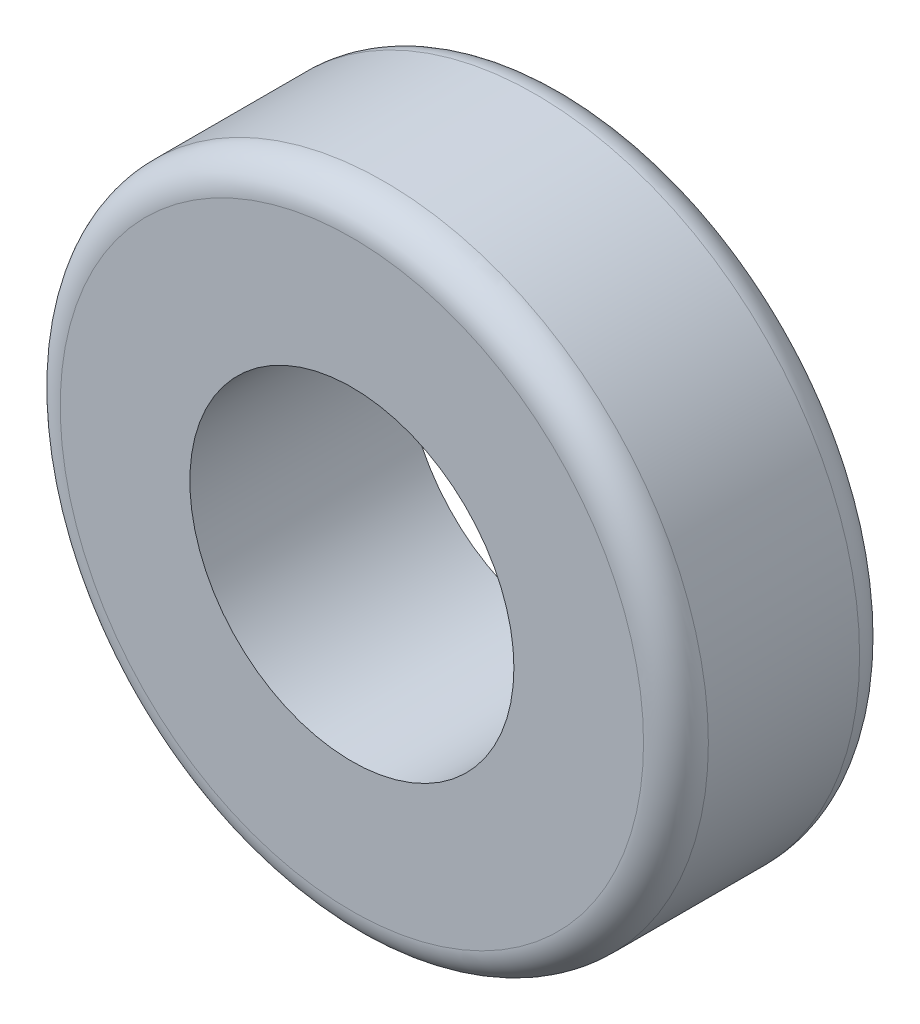
SolidWorks part; units mm, degrees
ref_plane "Front" through (0, 0, 0) normal (0, 0, 1) x (1, 0, 0)
ref_plane "Right" through (0, 0, 0) normal (0, 1, 0) x (1, 0, 0)
ref_plane "Sağ Düzlem" through (0, 0, 0) normal (1, 0, 0) x (0, 0, -1)
sketch "Sketch1" plane through (0, 0, 0) normal (0, 0, 1) x (1, 0, 0)
  circle A0 centre (0, 0) radius 15
  circle A1 centre (0, 0) radius 30
extrude "Boss-Extrude1" add sketch "Sketch1" along normal blind 20
fillet "Fillet1" radius 3 2 edges at (30, 0, 0) (30, 0, 20)
